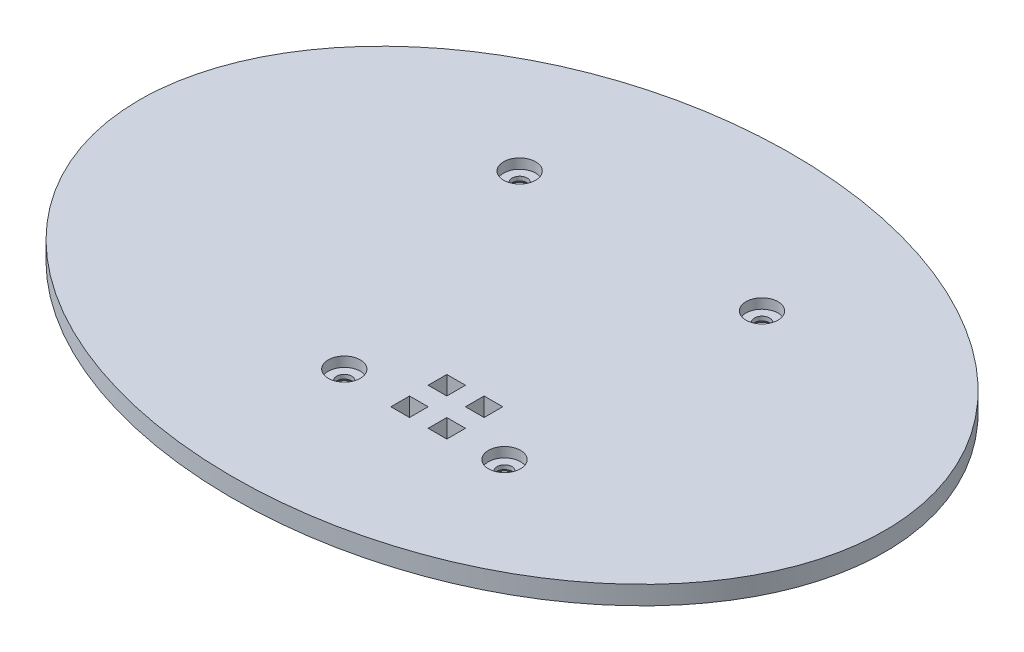
SolidWorks part; units mm, degrees
ref_plane "Front Plane" through (0, 0, 0) normal (0, 0, 1) x (1, 0, 0)
ref_plane "Top Plane" through (0, 0, 0) normal (0, 1, 0) x (1, 0, 0)
ref_plane "Right Plane" through (0, 0, 0) normal (1, 0, 0) x (0, 0, -1)
sketch "Sketch2" plane through (0, 0, 0) normal (0, 1, 0) x (1, 0, 0)
  ellipse E0 centre (0, 0) end of major axis (-50.8, 0) minor radius 38.1
  dimension "D1" = 50.8
  dimension "D2" = 38.1
extrude "top" add sketch "Sketch2" along normal blind 2.54
sketch "pcb size" plane through (0, 2.54, 0) normal (0, 1, 0) x (1, 0, 0)
  line L1 (20.32, -21.59) -> (-20.32, -21.59)
  line L2 (20.32, -21.59) -> (20.32, 21.59)
  line L3 (20.32, 21.59) -> (-20.32, 21.59)
  line L4 (-20.32, -21.59) -> (-20.32, 21.59)
  line L5 (20.32, -21.59) -> (-20.32, 21.59) construction
  line L6 (20.32, 21.59) -> (-20.32, -21.59) construction
  point P0 (0, 0)
  dimension "D1" = 43.18
sketch "Sketch4" plane through (0, 2.54, 0) normal (0, 1, 0) x (1, 0, 0)
  line L0 (20.32, -21.59) -> (20.32, 21.59) construction
  line L1 (10.16, -19.05) -> (7.62, -19.05)
  line L2 (10.16, -19.05) -> (10.16, -16.51)
  line L3 (10.16, -16.51) -> (7.62, -16.51)
  line L4 (7.62, -19.05) -> (7.62, -16.51)
  line L5 (20.32, -21.59) -> (-20.32, -21.59) construction
  line L7 (10.16, -13.97) -> (7.62, -13.97)
  line L8 (10.16, -13.97) -> (10.16, -11.43)
  line L9 (10.16, -11.43) -> (7.62, -11.43)
  line L10 (7.62, -13.97) -> (7.62, -11.43)
  line L11 (5.08, -16.51) -> (2.54, -16.51)
  line L12 (5.08, -16.51) -> (5.08, -19.05)
  line L13 (5.08, -19.05) -> (2.54, -19.05)
  line L14 (2.54, -16.51) -> (2.54, -19.05)
  line L15 (5.08, -13.97) -> (2.54, -13.97)
  line L16 (5.08, -13.97) -> (5.08, -11.43)
  line L17 (5.08, -11.43) -> (2.54, -11.43)
  line L18 (2.54, -13.97) -> (2.54, -11.43)
  dimension "D1" = 10.16
  dimension "D2" = 2.54
  dimension "D3" = 2.54
  dimension "D4" = 2.54
  dimension "D5" = 2.54
  dimension "D6" = 2.54
  dimension "D7" = 2.54
  dimension "D8" = 2.54
  dimension "D9" = 2.54
  dimension "D10" = 2.54
extrude "buttons" cut sketch "Sketch4" against normal blind 2.54
hole_wizard "CBORE for #1 Pan Head Machine Screw1" positions "Sketch6" profile "Sketch5" counterbore size "#1" standard "ANSI Inch" end condition through all
sketch "Sketch6" plane through (0, 2.54, 0) normal (0, 1, 0) x (1, 0, 0)
  line L0 (20.32, -21.59) -> (-20.32, 21.59) construction
  line L1 (20.32, 21.59) -> (-20.32, -21.59) construction
  line L2 (-20.32, -21.59) -> (-20.32, 21.59) construction
  line L3 (20.32, -21.59) -> (20.32, 21.59) construction
  line L4 (20.32, -21.59) -> (-20.32, -21.59) construction
  point P0 (-5.08, -17.78)
  point P2 (16.51, -17.5419)
  point P6 (16.51, 17.5419)
  point P10 (-16.51, 17.5419)
  dimension "D1" = 3.81
  dimension "D2" = 3.81
  dimension "D3" = 3.81
  dimension "D4" = 15.24
  dimension "D5" = 3.81
sketch "Sketch5" plane through (-5.08, 2.54, 17.78) normal (1, 0, 0) x (0, 0, 1)
  line L0 (0, 0) -> (0, 2.54)
  line L1 (1.0287, 1.905) -> (1.6637, 2.54)
  line L2 (1.0287, 1.905) -> (1.0287, 1.3462)
  line L3 (1.0287, 1.3462) -> (2.1831, 1.3462)
  line L4 (2.1831, 1.3462) -> (2.1831, 0)
  line L5 (2.1831, 0) -> (0, 0)
  line L11 (0, -6.35) -> (0, 107.95) construction
  line L12 (1.6637, 2.54) -> (0, 2.54)
  line L13 (-1.0287, 1.905) -> (-1.6637, 2.54) construction
  dimension "Thru Hole Dia." = 2.0574
  dimension "Thru Hole Depth" = 2.54
  dimension "C'Bore Dia." = 4.3663
  dimension "C'Bore Depth" = 1.3462
  dimension "Far C'Sink Dia." = 3.3274
  dimension "Far C'Sink Angle" = 90
